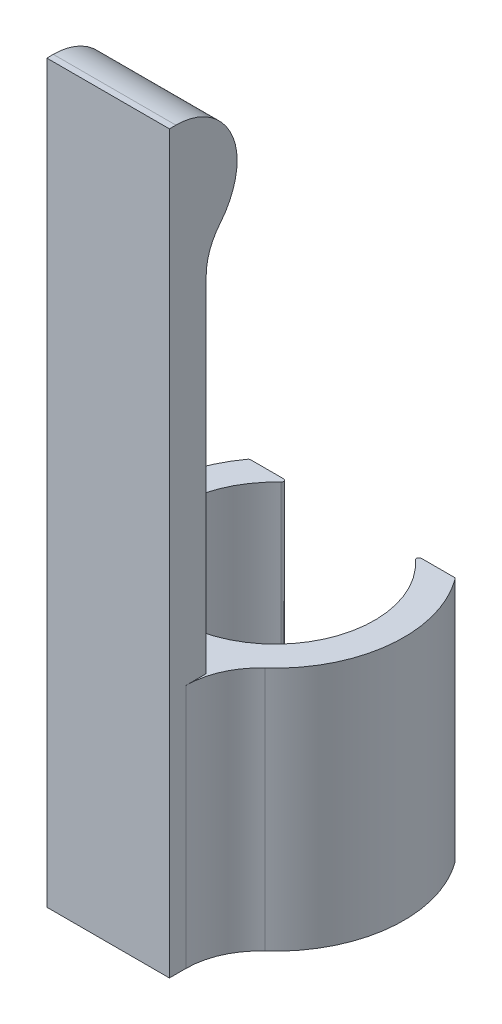
SolidWorks part; units mm, degrees
ref_plane "Front Plane" through (0, 0, 0) normal (0, 0, 1) x (1, 0, 0)
ref_plane "Top Plane" through (0, 0, 0) normal (0, 1, 0) x (1, 0, 0)
ref_plane "Right Plane" through (0, 0, 0) normal (1, 0, 0) x (0, 0, -1)
sketch "Sketch1" plane through (0, 0, 0) normal (0, 1, 0) x (1, 0, 0)
  line L0 (0, 0) -> (-3.2998, 4.0833)
  line L1 (0, 0) -> (0, 15.5575) construction
  line L2 (0, 0) -> (3.2998, 4.0833)
  line L3 (-2.5456, 3.15) -> (-4.2, 3.15)
  line L4 (2.5456, 3.15) -> (4.2, 3.15)
  line L5 (-2.5, -4.6165) -> (-2.5, -6.8165)
  line L6 (-2.5, -6.8165) -> (2.5, -6.8165)
  line L7 (2.5, -6.8165) -> (2.5, -4.6165)
  line L8 (-2.5, -4.6165) -> (2.5, -4.6165)
  line L9 (-2.5, -5.3165) -> (2.5, -5.3165)
  circle A0 centre (0, 0) radius 4.05
  circle A1 centre (0, 0) radius 5.25
  dimension "D3" = 8.1
  dimension "D2" = 7.2
  dimension "D4" = 2.2
  dimension "D5" = 5
  dimension "D6" = 1.5
  dimension "D1" = 1.2
extrude "Boss-Extrude1" add sketch "Sketch1" along normal blind 10 contours L8 A1 L4 A0 L3 | L7 L8 L5 L6 region at (-1.8017, 0, 3.7724)
fillet "Fillet3" radius 3 2 edges at (2.5, 5, 4.6165) (-2.5, 5, 4.6165)
extrude "Boss-Extrude2" add sketch "Sketch1<3>" along normal blind 30 contours L9 L5 L6 L7 region at (0, 0, 6.0665)
sketch "Sketch1<3>" plane through (0, 0, 0) normal (0, 1, 0) x (1, 0, 0) same geometry as "Sketch1"
sketch "Sketch2" plane through (0, 0, 0) normal (-1, 0, 0) x (0, 0, 1)
  line L3 (4.05, 10) -> (4.05, 27.5515) construction
  line L6 (5.3165, 25.103) -> (5.3165, 30)
  line L7 (5.3165, 30) -> (5.3165, 10) construction
  arc A0 (5.3165, 30) -> (5.3165, 25.103) centre (7.05, 27.5515) ccw
  point P3 (0, 0)
  point P4 (0, 0)
  point P9 (0, 0)
  point P10 (5.2596, 30)
  dimension "D1" = 3
extrude "Boss-Extrude3" add sketch "Sketch2" along normal mid plane 5
fillet "Fillet1" radius 2.5 2 edges at (0, 25.103, 5.3165) (0, 30, 5.3165)
fillet "Fillet4" radius 0.1 4 edges at (4.2, 5, -3.15) (-4.2, 5, -3.15) (-2.5456, 5, -3.15) (2.5456, 5, -3.15)
